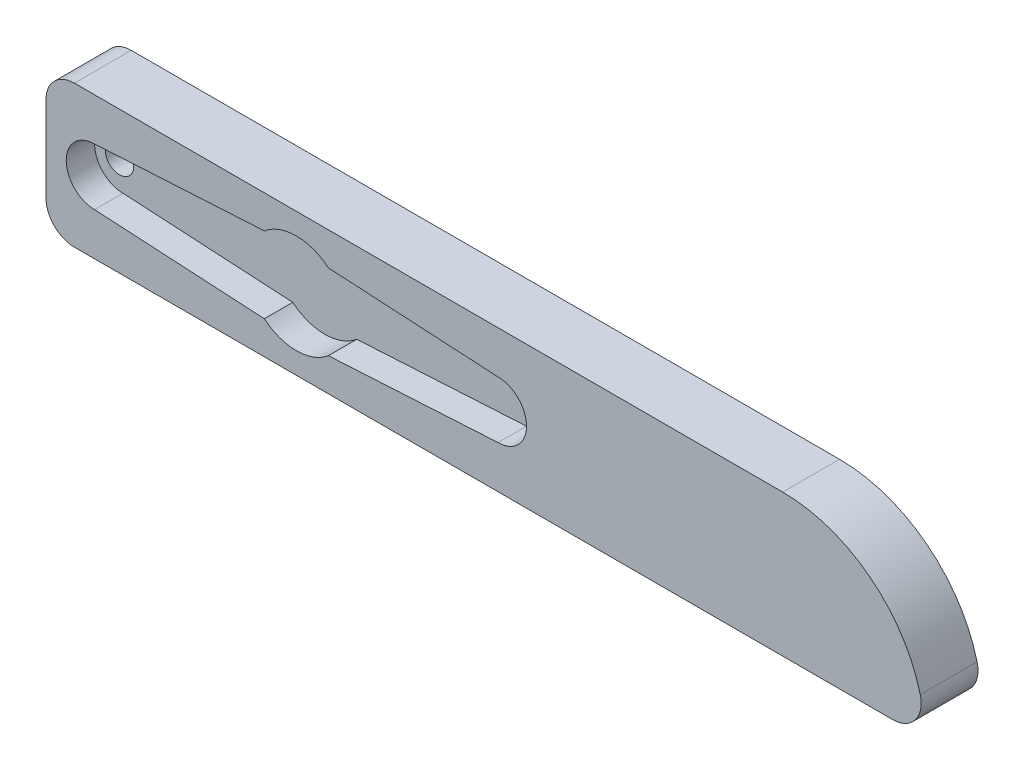
SolidWorks part; units mm, degrees
ref_plane "Front Plane" through (0, 0, 0) normal (0, 0, 1) x (1, 0, 0)
ref_plane "Top Plane" through (0, 0, 0) normal (0, 1, 0) x (1, 0, 0)
ref_plane "Right Plane" through (0, 0, 0) normal (1, 0, 0) x (0, 0, -1)
sketch "Sketch1" plane through (0, 0, 0) normal (0, 0, 1) x (1, 0, 0)
  line L1 (-25, -5) -> (25, -5)
  line L2 (-25, -5) -> (-25, 5)
  line L3 (-25, 5) -> (25, 5)
  line L4 (25, -5) -> (25, 5)
  line L5 (-25, -5) -> (25, 5) construction
  line L6 (-25, 5) -> (25, -5) construction
  point P0 (0, 0)
  dimension "D1" = 50
  dimension "D2" = 10
extrude "Boss-Extrude1" add sketch "Sketch1" along normal blind 4
sketch "Sketch2" plane through (0, 0, 4) normal (0, 0, 1) x (1, 0, 0)
  line L0 (-25, 0) -> (25, 0) construction
  line L1 (-25, 5) -> (-25, -5) construction
  line L2 (25, -5) -> (25, 5) construction
  line L3 (0, -5) -> (0, 5) construction
  line L4 (-25, -5) -> (25, -5) construction
  line L5 (25, 5) -> (-25, 5) construction
  line L6 (-2.2545, 2.6771) -> (-14.2, 2)
  line L7 (-2.2545, -2.6771) -> (-14.2, -2)
  line L8 (2.2545, -2.6771) -> (14.2, -2)
  line L9 (2.2545, 2.6771) -> (14.2, 2)
  arc A0 (-2.2545, -2.6771) -> (2.2545, -2.6771) centre (0, 0) ccw
  arc A1 (-14.2, 2) -> (-14.2, -2) centre (-14.2, 0) ccw
  arc A3 (14.2, 2) -> (14.2, -2) centre (14.2, 0) cw
  arc A4 (2.2545, 2.6771) -> (-2.2545, 2.6771) centre (0, 0) ccw
  point P15 (-16.2, 0)
  point P16 (16.2, 0)
  point P17 (0, 3.5)
  point P20 (-2.2545, 2.6771)
  point P23 (-14.45, 0)
  dimension "D1" = 7
  dimension "D4" = 4
  dimension "D2" = 16.2
  dimension "D3" = 16.2
  dimension "D5" = 2.4
  dimension "D6" = 14.45
extrude "Cut-Extrude1" cut sketch "Sketch2" against normal blind 2
sketch "Sketch3" plane through (0, 0, 2) normal (0, 0, 1) x (1, 0, 0)
  line L0 (-16.2, 0) -> (16.2, 0) construction
  line L1 (0, -3.5) -> (0, 3.5) construction
  arc A0 (-14.2, 2) -> (-14.2, -2) centre (-14.2, 0) ccw construction
  arc A1 (14.2, -2) -> (14.2, 2) centre (14.2, 0) ccw construction
  arc A2 (-2.2545, -2.6771) -> (2.2545, -2.6771) centre (0, 0) ccw construction
  arc A3 (2.2545, 2.6771) -> (-2.2545, 2.6771) centre (0, 0) ccw construction
  circle A4 centre (-14.45, 0) radius 1
  circle A5 centre (14.45, 0) radius 1
  point P16 (-14.45, 0)
  dimension "D2" = 2
  dimension "D1" = 14.45
extrude "Cut-Extrude2" cut sketch "Sketch3" against normal up to next
sketch "Sketch4" plane through (0, 0, 4) normal (0, 0, 1) x (1, 0, 0)
  line L1 (-26.3341, 7.4607) -> (-17.6216, 7.4607)
  line L2 (-26.3341, 7.4607) -> (-26.3341, -7.7249)
  line L3 (-26.3341, -7.7249) -> (-17.6216, -7.7249)
  line L4 (-17.6216, 7.4607) -> (-17.6216, -7.7249)
extrude "Cut-Extrude3" cut sketch "Sketch4" against normal up to next
sketch "Sketch5" plane through (0, 0, 4) normal (0, 0, 1) x (1, 0, 0)
  line L0 (-17.6216, -5) -> (25, -5) construction
  line L1 (25, 5) -> (44.2352, 5)
  line L2 (25, 5) -> (25, -5)
  line L3 (25, -5) -> (44.2352, -5)
  line L4 (44.2352, 5) -> (44.2352, -5)
  line L5 (25, 5) -> (-17.6216, 5) construction
extrude "Boss-Extrude2" add sketch "Sketch5" against normal blind 4
fillet "Fillet1" radius 10 1 edges at (44.2352, 5, 2)
fillet "Fillet2" radius 2 1 edges at (44.2352, -5, 2)
fillet "Fillet3" radius 2 1 edges at (-17.6216, 5, 2)
fillet "Fillet4" radius 2 1 edges at (-17.6216, -5, 2)
